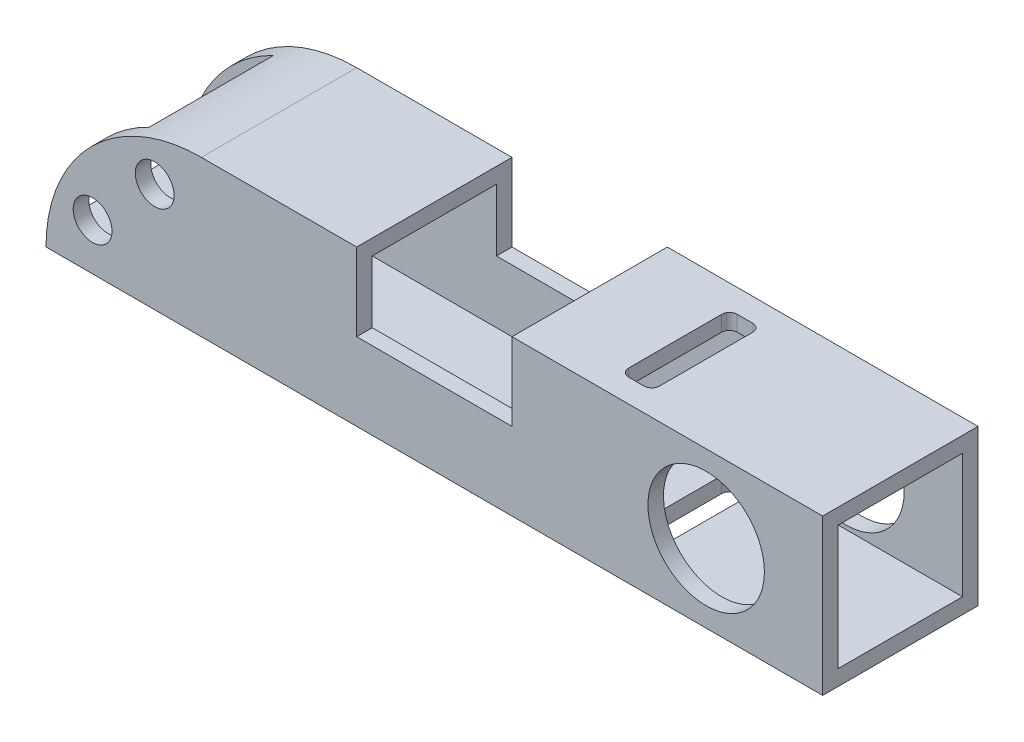
SolidWorks part; units mm, degrees
material "Plain Carbon Steel"
ref_plane "Front Plane" through (0, 0, 0) normal (0, 0, 1) x (1, 0, 0)
ref_plane "Top Plane" through (0, 0, 0) normal (0, 1, 0) x (1, 0, 0)
ref_plane "Right Plane" through (0, 0, 0) normal (1, 0, 0) x (0, 0, -1)
sketch "Sketch1" plane through (0, 0, 0) normal (1, 0, 0) x (0, 0, -1)
  line L1 (0, 0) -> (25.4, 0)
  line L2 (0, 0) -> (0, 25.4)
  line L3 (0, 25.4) -> (25.4, 25.4)
  line L4 (25.4, 0) -> (25.4, 25.4)
  line L5 (2.54, 22.86) -> (22.86, 22.86)
  line L6 (2.54, 22.86) -> (2.54, 2.54)
  line L7 (2.54, 2.54) -> (22.86, 2.54)
  line L8 (22.86, 22.86) -> (22.86, 2.54)
  dimension "D1" = 25.4
  dimension "D2" = 25.4
  dimension "D3" = 2.54
  dimension "D4" = 2.54
  dimension "D5" = 2.54
  dimension "D6" = 2.54
extrude "Boss-Extrude1" add sketch "Sketch1" along normal blind 127
sketch "Sketch2" plane through (0, 0, 0) normal (0, 0, 1) x (1, 0, 0)
  line L0 (127, 25.4) -> (0, 25.4) construction
  line L1 (50.8, 25.4) -> (76.2, 25.4)
  line L2 (50.8, 25.4) -> (50.8, 12.7)
  line L3 (50.8, 12.7) -> (76.2, 12.7)
  line L4 (76.2, 25.4) -> (76.2, 12.7)
  line L5 (127, 25.4) -> (127, 0) construction
  dimension "D1" = 12.7
  dimension "D2" = 25.4
  dimension "D3" = 50.8
extrude "Cut-Extrude1" cut sketch "Sketch2" against normal blind 127
fillet "Fillet1" radius 25.4 1 edges at (0, 25.4, -12.7)
sketch "Sketch3" plane through (0, 0, 0) normal (0, 0, 1) x (1, 0, 0)
  line L0 (127, 0) -> (0, 0) construction
  circle A0 centre (7.62, 7.62) radius 3.175
  circle A1 centre (17.78, 17.78) radius 3.175
  dimension "D1" = 7.62
  dimension "D3" = 17.78
  dimension "D2" = 7.62
  dimension "D4" = 17.78
extrude "Cut-Extrude2" cut sketch "Sketch3" against normal blind 127
sketch "Sketch4" plane through (0, 0, 0) normal (0, 0, 1) x (1, 0, 0)
  line L0 (127, 25.4) -> (127, 0) construction
  circle A0 centre (107.95, 12.7) radius 9.525
  dimension "D1" = 19.05
extrude "Cut-Extrude3" cut sketch "Sketch4" against normal blind 127
sketch "Sketch5" plane through (0, 0, 0) normal (0, -1, 0) x (1, 0, 0)
  line L0 (127, 0) -> (0, 0) construction
  line L1 (127, 0) -> (127, -25.4) construction
  line L2 (127, -25.4) -> (0, -25.4) construction
  line L3 (92.71, -3.81) -> (92.71, -21.59) construction
  line L4 (91.44, -3.81) -> (93.98, -3.81)
  line L5 (90.17, -5.08) -> (90.17, -20.32)
  line L6 (91.44, -21.59) -> (93.98, -21.59)
  line L7 (95.25, -5.08) -> (95.25, -20.32)
  arc A2 (91.44, -21.59) -> (90.17, -20.32) centre (91.44, -20.32) cw
  arc A3 (93.98, -21.59) -> (95.25, -20.32) centre (93.98, -20.32) ccw
  arc A4 (95.25, -5.08) -> (93.98, -3.81) centre (93.98, -5.08) ccw
  arc A5 (91.44, -3.81) -> (90.17, -5.08) centre (91.44, -5.08) ccw
  dimension "D5" = 1.27
  dimension "D6" = 5.08
  dimension "D7" = 3.81
  dimension "D8" = 3.81
  dimension "D9" = 34.29
extrude "Cut-Extrude4" cut sketch "Sketch5" against normal blind 127
